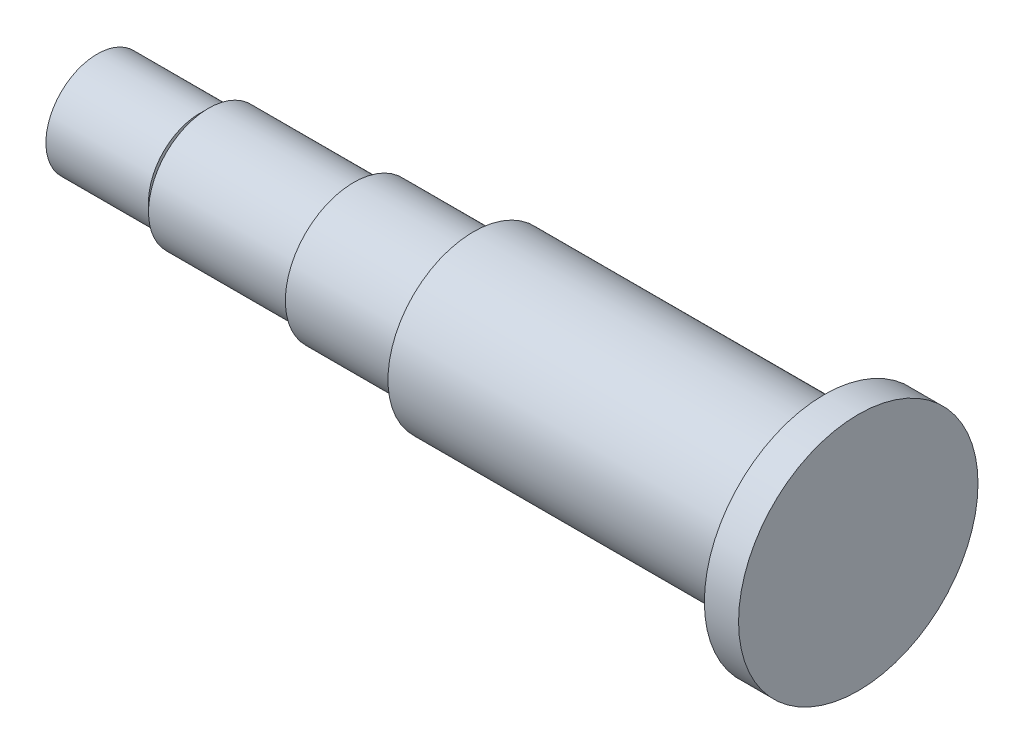
SolidWorks part; units mm, degrees
ref_plane "前视基准面" through (0, 0, 0) normal (0, 0, 1) x (1, 0, 0)
ref_plane "上视基准面" through (0, 0, 0) normal (0, 1, 0) x (1, 0, 0)
ref_plane "右视基准面" through (0, 0, 0) normal (1, 0, 0) x (0, 0, -1)
other "Configuration Table"
sketch "草图1" plane through (0, 0, 0) normal (0, 0, 1) x (1, 0, 0)
  line L0 (0, 0) -> (-8.425, 0) construction
  line L1 (0, 0) -> (0, 6)
  line L2 (0, 6) -> (12, 6)
  line L3 (12, 6) -> (12, 5)
  line L4 (12, 5) -> (13, 5)
  line L5 (13, 5) -> (13, 7)
  line L6 (13, 7) -> (30, 7)
  line L7 (30, 7) -> (30, 8)
  line L8 (30, 8) -> (44, 8)
  line L9 (44, 8) -> (44, 10)
  line L10 (44, 10) -> (84, 10)
  line L11 (84, 10) -> (84, 9)
  line L12 (84, 9) -> (85, 9)
  line L13 (85, 9) -> (85, 14)
  line L14 (85, 14) -> (89, 14)
  line L16 (0, 0) -> (89, 0)
  line L21 (89, 14) -> (89, 0)
  dimension "D1" = 12
  dimension "D2" = 16
  dimension "D3" = 28
  dimension "D4" = 20
  dimension "D5" = 14
  dimension "D6" = 17
  dimension "D7" = 40
  dimension "D8" = 55
  dimension "D9" = 1
  dimension "D10" = 1
  dimension "D11" = 85
  dimension "D12" = 1
  dimension "D13" = 1
  dimension "D14" = 4
revolve "旋转1" add sketch "草图1" angle 360 about L0
ref_plane "基准面1" through (28, 0, 0) normal (-1, 0, 0) x (0, 0, 1)
sketch "草图2" plane through (28, 0, 0) normal (-1, 0, 0) x (0, 0, 1)
  line L1 (-7.5499, 2.5) -> (-3, 2.5)
  line L2 (-7.5499, 2.5) -> (-7.5499, -2.5)
  line L3 (-7.5499, -2.5) -> (-3, -2.5)
  line L4 (-3, 2.5) -> (-3, -2.5)
  line L5 (-7.5499, 2.5) -> (-3, -2.5) construction
  line L6 (-7.5499, -2.5) -> (-3, 2.5) construction
  circle A1 centre (0, 0) radius 8 construction
  point P0 (-5.2749, 0)
  point P6 (0, 0)
  dimension "D1" = 11
  dimension "D2" = 5
extrude "切除-拉伸1" cut sketch "草图2" along normal blind 12
fillet "圆角1" 2 edges at (16, 2.5, -4.7692) (16, -2.5, -4.7692) type full round first side face at (22, 2.5, -4.7692) second side face at (22, -2.5, -4.7692) middle face at (16, 0, -4.8846)
fillet "圆角2" 2 edges at (28, 2.5, -4.7692) (28, -2.5, -4.7692) type full round first side face at (23.25, 2.5, -4.7692) second side face at (23.25, -2.5, -4.7692) middle face at (28, 0, -4.8846)
